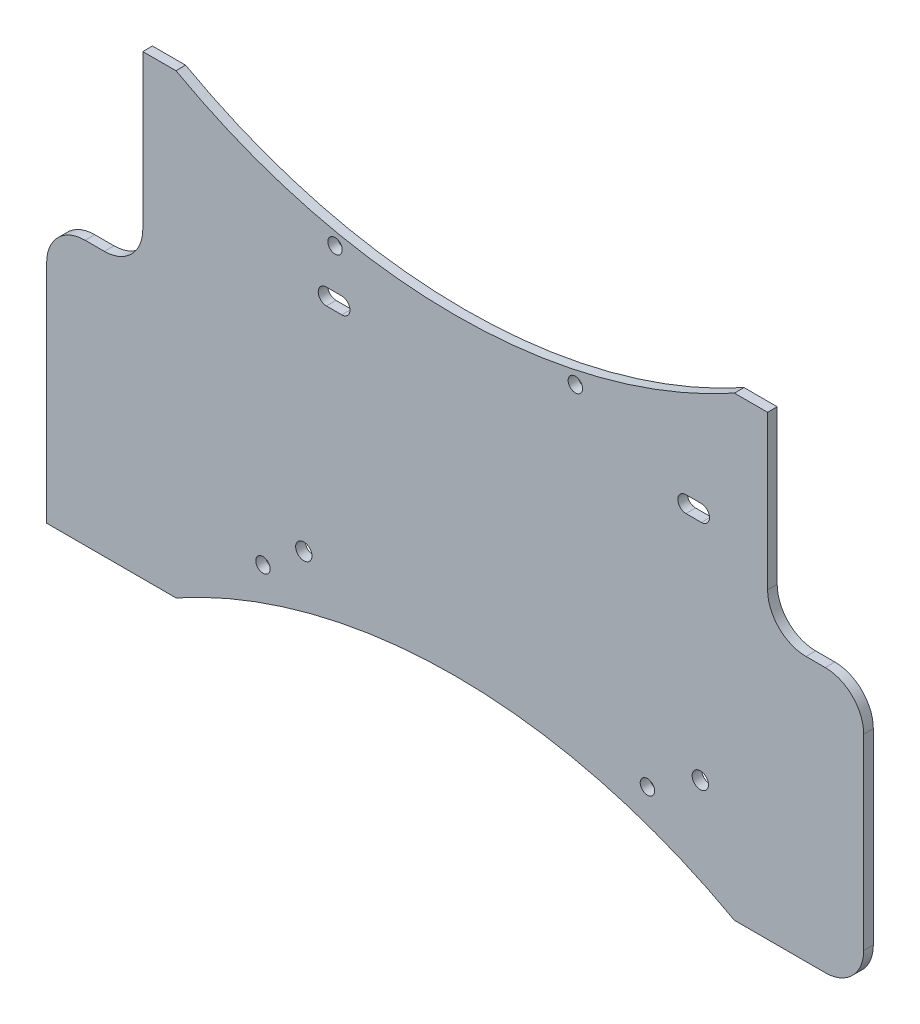
SolidWorks part; units mm, degrees
ref_plane "Front Plane" through (0, 0, 0) normal (0, 0, 1) x (1, 0, 0)
ref_plane "Top Plane" through (0, 0, 0) normal (0, 1, 0) x (1, 0, 0)
ref_plane "Right Plane" through (0, 0, 0) normal (1, 0, 0) x (0, 0, -1)
sketch "Sketch2" plane through (0, 0, 0) normal (0, 0, 1) x (1, 0, 0)
  line L0 (0, 47.5) -> (0, -47.5) construction
  line L1 (83.5779, 0) -> (-83.5779, 0) construction
  line L2 (65, 47.5) -> (58.0948, 47.5)
  line L3 (85, -47.5) -> (58.0948, -47.5)
  line L4 (-85, 7.5) -> (-85, -47.5)
  line L5 (85, 7.5) -> (85, -47.5)
  line L6 (83.5779, 47.5) -> (-83.5779, 47.5) construction
  line L7 (0, 54.5558) -> (0, -54.5558) construction
  line L8 (83.5779, -47.5) -> (-83.5779, -47.5) construction
  line L9 (-65, 47.5) -> (-65, 7.5)
  line L10 (-58.0948, -47.5) -> (-85, -47.5)
  line L11 (65, 47.5) -> (65, 7.5)
  line L12 (-85, 54.5558) -> (-85, -54.5558) construction
  line L13 (85, 7.5) -> (85, -47.5)
  line L14 (-65, 54.5558) -> (-65, -54.5558) construction
  line L15 (0, -152.5) -> (0, -156.1201) construction
  line L16 (85, 54.5558) -> (85, -54.5558) construction
  line L17 (-65, 7.5) -> (-85, 7.5)
  line L18 (65, 7.5) -> (85, 7.5)
  line L19 (65, 47.5) -> (65, -49.1815)
  line L20 (-58.0948, 47.5) -> (-65, 47.5)
  line L21 (-25.2, 25) -> (-25.2, 9.1617) construction
  line L22 (-90.3126, 22.46) -> (57.643, 22.46) construction
  line L23 (49.8, 39.3402) -> (49.8, 9.1617) construction
  line L24 (48.0152, 22.46) -> (51.2152, 22.46) construction
  line L25 (48.0152, 24.16) -> (51.2152, 24.16)
  line L26 (48.0152, 20.76) -> (51.2152, 20.76)
  line L27 (-26.8, 22.46) -> (-23.6, 22.46) construction
  line L28 (-26.8, 24.16) -> (-23.6, 24.16)
  line L29 (-26.8, 20.76) -> (-23.6, 20.76)
  arc A0 (58.0948, -47.5) -> (-58.0948, -47.5) centre (0, -152.5) ccw
  arc A1 (-58.0948, 47.5) -> (58.0948, 47.5) centre (0, 152.5) ccw
  circle A2 centre (-40, -32.5) radius 1.5
  circle A3 centre (40, -32.5) radius 1.5
  circle A4 centre (-25, 32.5) radius 1.5
  circle A5 centre (25, 32.5) radius 1.5
  arc A6 (48.0152, 24.16) -> (48.0152, 20.76) centre (48.0152, 22.46) ccw
  circle A7 centre (51, -25.8) radius 1.7
  circle A8 centre (-31.5, -25.8) radius 1.7
  arc A9 (-26.8, 24.16) -> (-26.8, 20.76) centre (-26.8, 22.46) ccw
  arc A10 (51.2152, 20.76) -> (51.2152, 24.16) centre (51.2152, 22.46) ccw
  arc A11 (-23.6, 20.76) -> (-23.6, 24.16) centre (-23.6, 22.46) ccw
  point P50 (49.6152, 22.46)
  point P59 (-25.2, 22.46)
  dimension "D7" = 120
  dimension "D6" = 240
  dimension "D10" = 65
  dimension "D15" = 3
  dimension "D14" = 3
  dimension "D23" = 1.7
  dimension "D24" = 3.4
  dimension "D25" = 50.8
  dimension "D26" = 3.4
  dimension "D27" = 3.2
  dimension "D17" = 1.7
  dimension "D3" = 152.5
  dimension "D8" = 55
  dimension "D9" = 152.5
  dimension "D11" = 25
  dimension "D12" = 32.5
  dimension "D13" = 32.5
  dimension "D16" = 40
  dimension "D18" = 90.2
  dimension "D19" = 14
  dimension "D20" = 96.5
  dimension "D21" = 3.2
  dimension "D22" = 82.5
  dimension "D1" = 47.5
  dimension "D2" = 47.5
  dimension "D4" = 85
  dimension "D5" = 20
extrude "Boss-Extrude1" add sketch "Sketch2" along normal blind 2 contours A1 L20 L9 L17 L4 L10 A0 L3 L5 L18 L11 L2 region at (-7.5541, -2.0372, 0)
fillet "Fillet4" radius 8 1 edges at (-85, 7.5, 1)
extrude "Boss-Extrude2" add sketch "Sketch2<3>" along normal blind 2 contours L18 L19 L3 L5 region at (75, -20, 0)
sketch "Sketch2<3>" plane through (0, 0, 0) normal (0, 0, 1) x (1, 0, 0) same geometry as "Sketch2"
fillet "Fillet6" radius 8 3 edges at (85, -47.5, 1) (85, 7.5, 1)
fillet "Fillet7" radius 8 1 edges at (-65, 7.5, 1)
